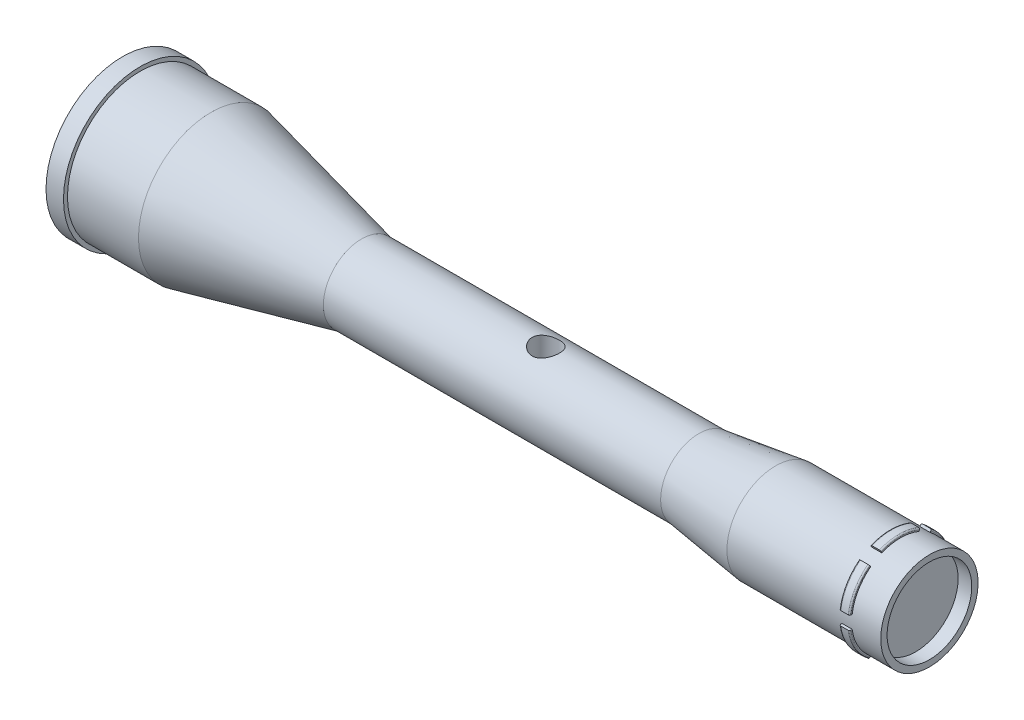
SolidWorks part; units mm, degrees
ref_plane "Front Plane" through (0, 0, 0) normal (0, 0, 1) x (1, 0, 0)
ref_plane "Top Plane" through (0, 0, 0) normal (0, 1, 0) x (1, 0, 0)
ref_plane "Right Plane" through (0, 0, 0) normal (1, 0, 0) x (0, 0, -1)
sketch "Sketch1" plane through (0, 0, 0) normal (0, 1, 0) x (1, 0, 0)
  line L0 (-147.75, 0) -> (147.75, 0) construction
  line L1 (-147.75, 0) -> (-147.75, 28.025)
  line L2 (-60.19, 14) -> (63.31, 14)
  line L3 (-147.75, 28.025) -> (-141.35, 28.025)
  line L4 (-141.35, 28.025) -> (-141.35, 26.56)
  line L5 (-141.35, 26.56) -> (-115.35, 26.56)
  line L6 (147.75, 0) -> (147.75, 17.82)
  line L7 (147.75, 17.82) -> (91.41, 17.82)
  line L8 (-60.19, 14) -> (-115.35, 26.56)
  line L9 (63.31, 14) -> (91.41, 17.82)
  line L10 (-147.75, 0) -> (147.75, 0)
  point P3 (0, 0)
  dimension "D1" = 295.5
  dimension "D2" = 28
  dimension "D3" = 123.5
  dimension "D4" = 6.4
  dimension "D5" = 28.025
  dimension "D6" = 26.56
  dimension "D7" = 26
  dimension "D8" = 35.64
  dimension "D9" = 28.1
  dimension "D10" = 55.16
revolve "Revolve1" add sketch "Sketch1" angle 360 about L0 other way angle 360
ref_plane "Plane1" through (137.11, 0, 0) normal (1, 0, 0) x (0, 0, -1)
sketch "Sketch2" plane through (137.11, 0, 0) normal (1, 0, 0) x (0, 0, -1)
  line L0 (0, 0) -> (-7.1753, 17.3227)
  line L1 (0, 0) -> (7.1753, 17.3227)
  line L2 (0, 0) -> (0, 18.75) construction
  line L3 (0, 0) -> (11.4143, 14.8754)
  line L4 (0, 0) -> (18.5896, 2.4474)
  line L5 (0, 0) -> (18.5896, -2.4474)
  line L6 (0, 0) -> (11.4143, -14.8754)
  line L7 (0, 0) -> (7.1753, -17.3227)
  line L8 (0, 0) -> (-7.1753, -17.3227)
  line L9 (0, 0) -> (-11.4143, -14.8754)
  line L10 (0, 0) -> (-18.5896, -2.4474)
  line L11 (0, 0) -> (-18.5896, 2.4474)
  line L12 (0, 0) -> (-11.4143, 14.8754)
  circle A0 centre (0, 0) radius 17.82 construction
  circle A1 centre (0, 0) radius 17.82
  circle A2 centre (0, 0) radius 18.75
  point P19 (0, 0)
  dimension "D1" = 37.5
  dimension "D2" = 45
  dimension "D3" = 22.5
  dimension "D4" = 6
extrude "Boss-Extrude1" add sketch "Sketch2" against normal blind 3.73 separate body contours L2 A1 L1 A2 | A1 L2 A2 L0 | L4 A2 L3 A1 | L6 A2 L5 A1 | L8 A2 L7 A1 | L10 A2 L9 A1 | L12 A2 L11 A1 region at (137.11, 17.8225, 3.5451) region at (137.11, 17.8225, -3.5451) region at (137.11, 8.9112, -15.4347) region at (137.11, -8.9112, -15.4347) region at (137.11, -17.8225, 0) region at (137.11, -8.9112, 15.4347) region at (137.11, 8.9112, 15.4347)
fillet "Fillet1" radius 0.5 2 edges at (133.38, 9.375, -16.238) (137.11, 9.375, -16.238)
fillet "Fillet2" radius 0.5 2 edges at (133.38, 18.75, 0) (137.11, 18.75, 0)
fillet "Fillet3" radius 0.5 2 edges at (133.38, 9.375, 16.238) (137.11, 9.375, 16.238)
fillet "Fillet4" radius 0.5 2 edges at (133.38, -9.375, 16.238) (137.11, -9.375, 16.238)
fillet "Fillet5" radius 0.5 2 edges at (137.11, -18.75, 0) (133.38, -18.75, 0)
fillet "Fillet6" radius 0.5 2 edges at (137.11, -9.375, -16.238) (133.38, -9.375, -16.238)
sketch "Sketch3" plane through (0, 0, 0) normal (0, 1, 0) x (1, 0, 0)
  line L0 (63.31, -14) -> (63.31, 14) construction
  circle A0 centre (7.27, 0) radius 5
  dimension "D2" = 10
  dimension "D1" = 56.04
extrude "Cut-Extrude1" cut sketch "Sketch3" against normal through all both and the other way through all
sketch "Sketch4" plane through (-147.75, 0, 0) normal (-1, 0, 0) x (0, 0, 1)
  circle A0 centre (0, 0) radius 25.25
  dimension "D1" = 50.5
extrude "Cut-Extrude2" cut sketch "Sketch4" against normal blind 5
sketch "Sketch5" plane through (147.75, 0, 0) normal (1, 0, 0) x (0, 0, -1)
  circle A0 centre (0, 0) radius 15.5
  dimension "D1" = 31
extrude "Cut-Extrude3" cut sketch "Sketch5" against normal blind 5
